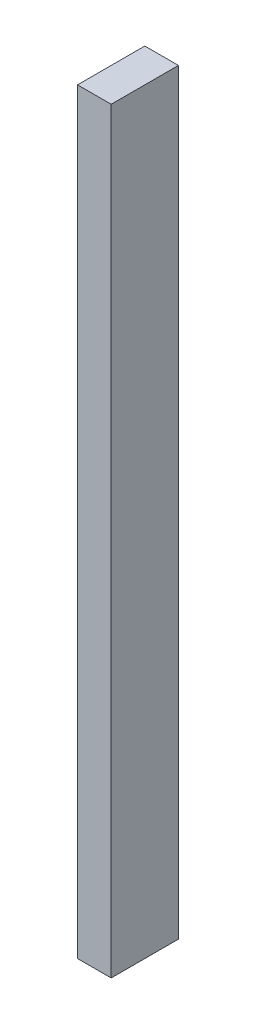
SolidWorks part; units mm, degrees
material "Pine"
ref_plane "Front Plane" through (0, 0, 0) normal (0, 0, 1) x (1, 0, 0)
ref_plane "Top Plane" through (0, 0, 0) normal (0, 1, 0) x (1, 0, 0)
ref_plane "Right Plane" through (0, 0, 0) normal (1, 0, 0) x (0, 0, -1)
sketch "Sketch1" plane through (0, 0, 0) normal (0, 1, 0) x (1, 0, 0)
  line L1 (0, 0) -> (40, 0)
  line L2 (0, 0) -> (0, 80)
  line L3 (0, 80) -> (40, 80)
  line L4 (40, 0) -> (40, 80)
  dimension "D1" = 80
  dimension "D2" = 40
extrude "Boss-Extrude1" add sketch "Sketch1" along normal blind 900
